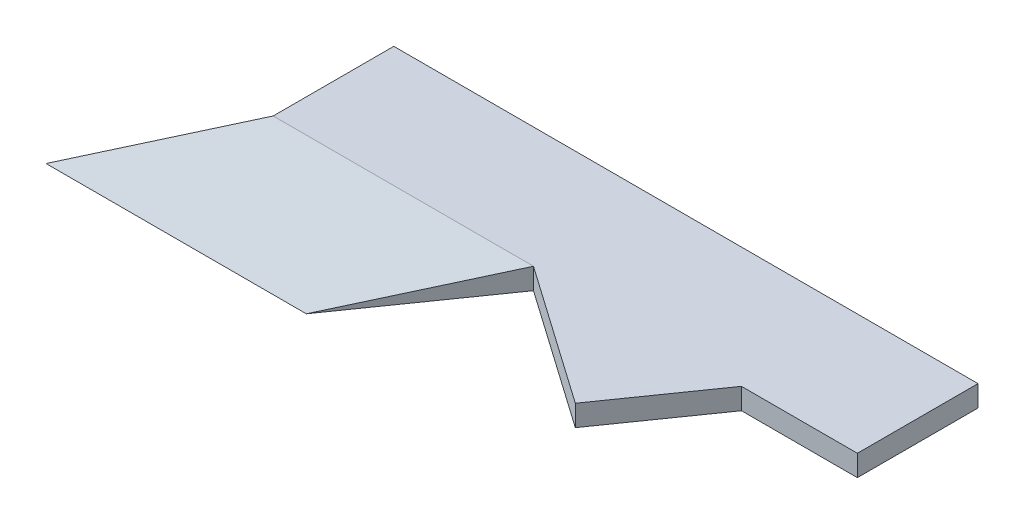
SolidWorks part; units mm, degrees
material "普通碳钢"
ref_plane "前视基准面" through (0, 0, 0) normal (0, 0, 1) x (1, 0, 0)
ref_plane "上视基准面" through (0, 0, 0) normal (0, 1, 0) x (1, 0, 0)
ref_plane "右视基准面" through (0, 0, 0) normal (1, 0, 0) x (0, 0, -1)
sketch "草图1" plane through (0, 0, 0) normal (0, 1, 0) x (1, 0, 0)
  line L0 (1664.94, -570) -> (1018.33, -1493.4547)
  line L1 (-2760.5, 570) -> (2760.5, 570)
  line L2 (-2760.5, 570) -> (-2760.5, -570)
  line L3 (-2760.5, -570) -> (2760.5, -570)
  line L4 (2760.5, 570) -> (2760.5, -570)
  line L5 (0, -570) -> (0, 570) construction
  line L6 (-2760.5, 0) -> (2760.5, 0) construction
  line L7 (1018.33, -1493.4547) -> (-300.5, -570)
  point P0 (0, 0)
  dimension "D1" = 5521
  dimension "D2" = 1140
  dimension "D3" = 1095.56
  dimension "D4" = 2460
  dimension "D5" = 125
extrude "凸台-拉伸1" add sketch "草图1" along normal blind 200 contours L7 L0 L3 | L2 L1 L4 L3 region at (794.2567, 0, 877.8182)
sketch "草图2" plane through (1385.0039, 0, 969.7902) normal (0.8192, 0, 0.5736) x (0.5736, 0, -0.8192)
  line L0 (-639.2764, 200) -> (-639.2764, 0)
  line L1 (-639.2764, 200) -> (-639.2764, 0) construction
  line L2 (-639.2764, 0) -> (-1902.0267, 0)
  line L3 (-1902.0267, 0) -> (-639.2764, 200)
  dimension "D1" = 9
extrude "凸台-拉伸2" [suppressed] add sketch "草图2" against normal up to next from vertex
sketch "草图3" plane through (-2760.5, 0, 0) normal (-1, 0, 0) x (0, 0, 1)
  line L0 (570, 200) -> (570, 0)
  line L1 (570, 0) -> (1832.7503, 0)
  line L2 (1832.7503, 0) -> (570, 200)
  dimension "D1" = 9
extrude "凸台-拉伸3" add sketch "草图3" against normal up to vertex (2460 mm away) and the other way blind 1000 up to point (-300.5, 200, 570)
sketch "草图4" plane through (0, 200, 0) normal (0, 1, 0) x (1, 0, 0)
  line L0 (-300.5, -570) -> (-1184.6873, -1832.7503)
  line L1 (-300.5, -1832.7503) -> (-3760.5, -1832.7503) construction
  line L2 (-1184.6873, -1832.7503) -> (134.1428, -2756.205)
  line L3 (-2760.5, -570) -> (-3644.6873, -1832.7503)
  line L4 (134.1428, -2756.205) -> (1018.33, -1493.4547)
  line L5 (1664.94, -570) -> (1018.33, -1493.4547) construction
  line L6 (-3760.5, -1832.7503) -> (-300.5, -1832.7503) construction
  line L7 (-3644.6873, -1832.7503) -> (-3760.5, -1832.7503)
  line L8 (-3760.5, -1832.7503) -> (-3760.5, -570)
  line L9 (-3760.5, -570) -> (-2760.5, -570)
  line M4 (-300.5, -570) -> (1018.33, -1493.4547)
extrude "切除-拉伸1" cut sketch "草图4" against normal through all contours L9 L8 L7 L3 | L2 L4 L0 M4 region at (-83.1786, 200, 1663.1025) region at (-3423.1598, 200, 1034.6047)
